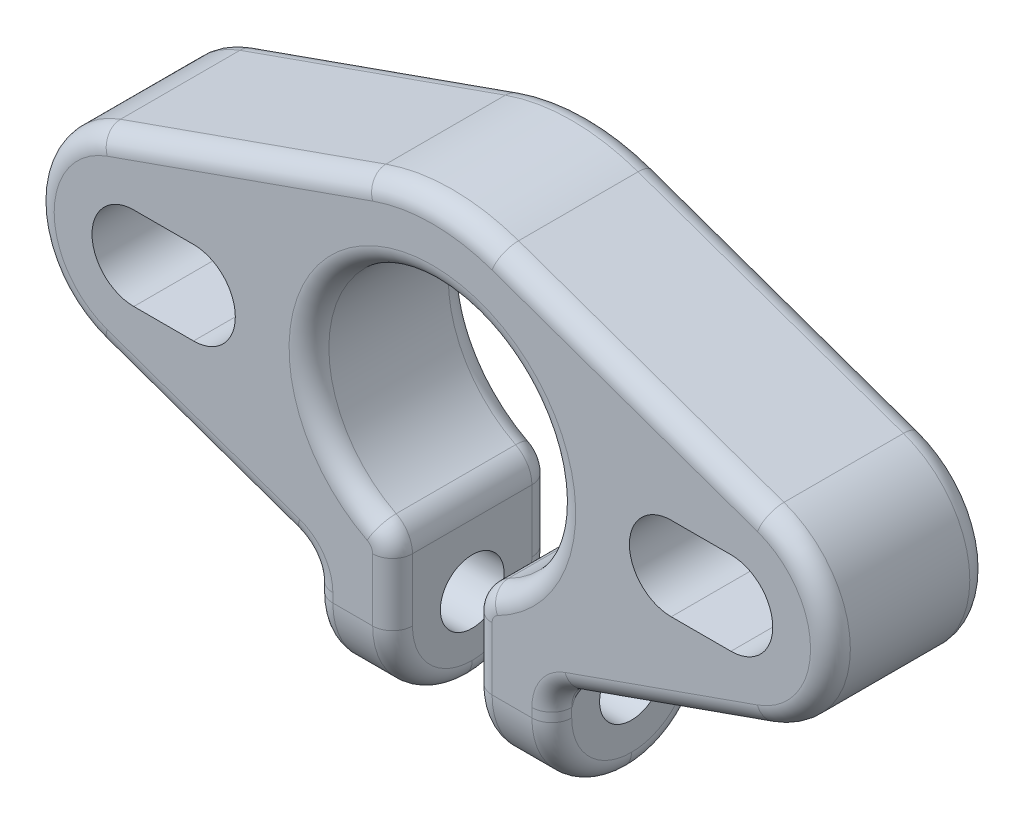
SolidWorks part; units mm, degrees
ref_plane "Спереди" through (0, 0, 0) normal (0, 0, 1) x (1, 0, 0)
ref_plane "Сверху" through (0, 0, 0) normal (0, 1, 0) x (1, 0, 0)
ref_plane "Справа" through (0, 0, 0) normal (1, 0, 0) x (0, 0, -1)
sketch "Эскиз1" plane through (0, 0, 0) normal (0, 0, 1) x (1, 0, 0)
  line L0 (-32.3801, 0) -> (35.5563, 0) construction
  line L1 (-15, 2.1) -> (-12, 2.1)
  line L2 (-15, -2.1) -> (-12, -2.1)
  line L3 (12, 2.1) -> (15, 2.1)
  line L4 (12, -2.1) -> (15, -2.1)
  line L5 (-3.3333, 9.4281) -> (-16.6667, 4.714)
  line L6 (3.3333, 9.4281) -> (16.6667, 4.714)
  line L7 (0, 14.3867) -> (0, -20.9882) construction
  line L8 (-2, -5.8686) -> (-2, -14)
  line L9 (2, -5.8686) -> (2, -14)
  line L10 (-6, -14) -> (-2, -14)
  line L11 (6, -14) -> (6, -8.4853)
  line L12 (-6, -14) -> (-6, -8.4853)
  line L13 (16.6667, -4.714) -> (6, -8.4853)
  line L14 (-16.6667, -4.714) -> (-6, -8.4853)
  line L15 (2, -14) -> (6, -14)
  arc A0 (2, -5.8686) -> (-2, -5.8686) centre (0, 0) ccw
  arc A1 (-15, 2.1) -> (-15, -2.1) centre (-15, 0) ccw
  arc A2 (15, -2.1) -> (15, 2.1) centre (15, 0) ccw
  arc A3 (-12, -2.1) -> (-12, 2.1) centre (-12, 0) ccw
  arc A4 (12, 2.1) -> (12, -2.1) centre (12, 0) ccw
  arc A5 (-16.6667, 4.714) -> (-16.6667, -4.714) centre (-15, 0) ccw
  arc A6 (16.6667, -4.714) -> (16.6667, 4.714) centre (15, 0) ccw
  arc A8 (3.3333, 9.4281) -> (-3.3333, 9.4281) centre (0, 0) ccw
  dimension "D1" = 12.4
  dimension "D2" = 4.2
  dimension "D7" = 10
  dimension "D3" = 15
  dimension "D4" = 15
  dimension "D5" = 3
  dimension "D6" = 3
  dimension "D9" = 2
  dimension "D10" = 2
  dimension "D11" = 14
  dimension "D12" = 4
  dimension "D13" = 4
extrude "Бобышка-Вытянуть1" add sketch "Эскиз1" along normal blind 8
fillet "Скругление4" radius 1.5 4 edges at (6, -8.4853, 4) (-6, -8.4853, 4) (-2, -5.8686, 4) (2, -5.8686, 4)
sketch "Эскиз2" plane through (6, 0, 0) normal (1, 0, 0) x (0, 0, -1)
  line L0 (-8, -14) -> (0, -14) construction
  line L1 (-4, -14) -> (-4, -8.7504) construction
  line L2 (-13.2293, -10) -> (5.0836, -10) construction
  line L4 (-0.8246, -10) -> (-2.4123, -7.25)
  line L5 (-2.4123, -7.25) -> (-5.5877, -7.25)
  line L6 (-5.5877, -7.25) -> (-7.1754, -10)
  line L7 (-7.1754, -10) -> (-5.5877, -12.75)
  line L8 (-5.5877, -12.75) -> (-2.4123, -12.75)
  line L9 (-2.4123, -12.75) -> (-0.8246, -10)
  circle A0 centre (-4, -10) radius 1.6
  circle A1 centre (-4, -10) radius 2.75 construction
  circle A2 centre (-4, -10) radius 3
  point P0 (-4, -14)
  point P6 (-4, -10)
  dimension "D2" = 3.2
  dimension "D3" = 6
  dimension "D1" = 4
extrude "Вырез-Вытянуть1" cut sketch "Эскиз2" against normal through all from offset 10 contours A0
extrude "Вырез-Вытянуть2" cut sketch "Эскиз2<3>" along normal through all contours A2
sketch "Эскиз2<3>" plane through (6, 0, 0) normal (1, 0, 0) x (0, 0, -1) same geometry as "Эскиз2"
extrude "Вырез-Вытянуть3" cut sketch "Эскиз2<4>" against normal through all from offset 12 contours L7 L8 L9 L4 L5 L6 offset against normal yes
sketch "Эскиз2<4>" plane through (6, 0, 0) normal (1, 0, 0) x (0, 0, -1) same geometry as "Эскиз2"
fillet "Скругление1" radius 4 4 edges at (4, -14, 8) (4, -14, 0) (-4, -14, 0) (-4, -14, 8)
fillet "Скругление2" radius 1 40 edges at (-2, -8.4293, 8) (-2, -8.4293, 0) (-2, -12.8284, 1.1716) (2, -8.4293, 0) (2, -12.8284, 1.1716) (2, -8.4293, 8) (11.8333, -6.4229, 0) (20, 0, 0) (10, 7.0711, 0) (0, 10, 0) (-10, 7.0711, 0) (-20, 0, 0) (6, -9.773, 8) (6, -9.773, 0) (6, -12.8284, 1.1716) (-6, -9.773, 0) (-6, -12.8284, 1.1716) (-6, -9.773, 8) (11.8333, -6.4229, 8) (20, 0, 8) (10, 7.0711, 8) (0, 10, 8) (-10, 7.0711, 8) (-20, 0, 8) (-2, -12.8284, 6.8284) (2, -12.8284, 6.8284) (-11.8333, -6.4229, 0) (6, -12.8284, 6.8284) (-6, -12.8284, 6.8284) (-11.8333, -6.4229, 8) (6.2753, -8.6799, 0) (6.2753, -8.6799, 8) (-6.2753, -8.6799, 0) (-6.2753, -8.6799, 8) (2.2208, -6.0752, 0) (0, 6.2, 0) (-2.2208, -6.0752, 0) (-2.2208, -6.0752, 8) (0, 6.2, 8) (2.2208, -6.0752, 8)
